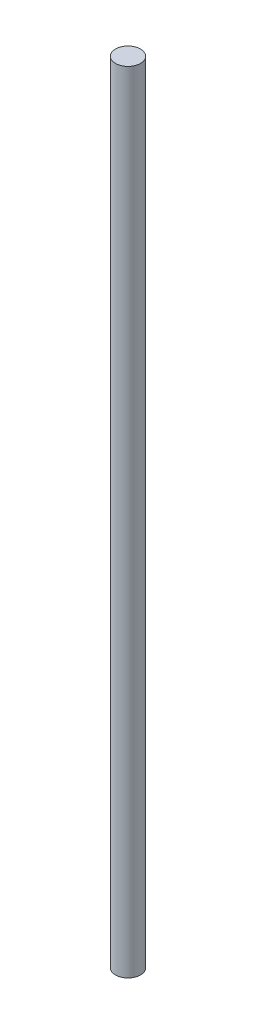
SolidWorks part; units mm, degrees
material "Copper"
ref_plane "Front Plane" through (0, 0, 0) normal (0, 0, 1) x (1, 0, 0)
ref_plane "Top Plane" through (0, 0, 0) normal (0, 1, 0) x (1, 0, 0)
ref_plane "Right Plane" through (0, 0, 0) normal (1, 0, 0) x (0, 0, -1)
sketch "Sketch1" plane through (0, 0, 0) normal (0, 1, 0) x (1, 0, 0)
  circle A0 centre (0, 0) radius 1.5875
  dimension "D1" = 3.175
extrude "Boss-Extrude1" add sketch "Sketch1" along normal blind 100.33
